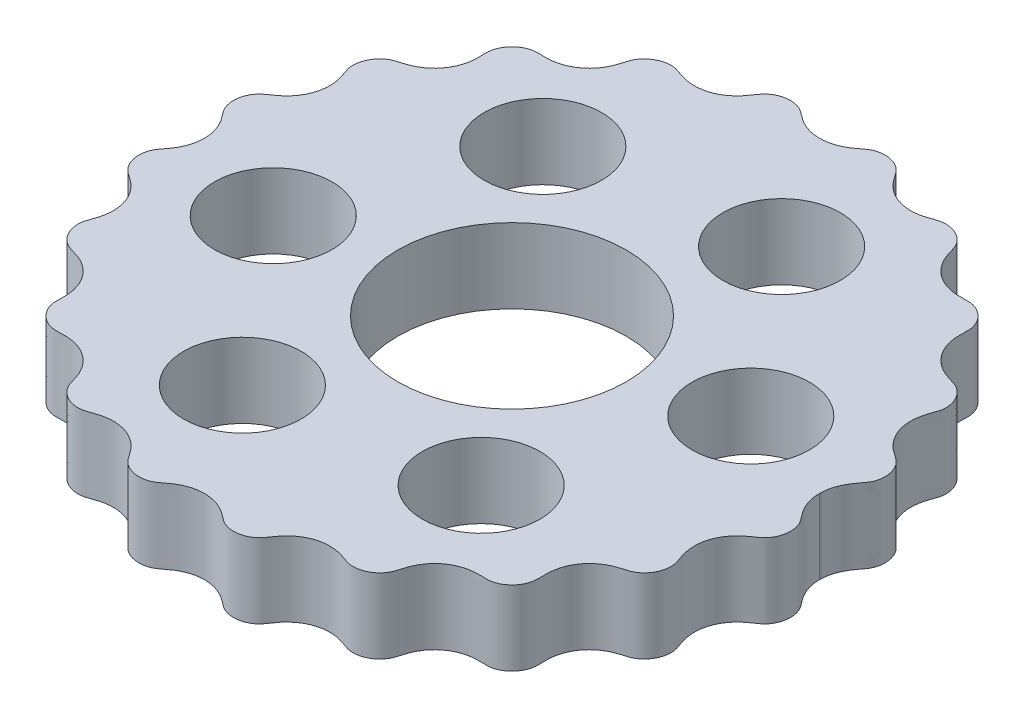
SolidWorks part; units mm, degrees
ref_plane "Front Plane" through (0, 0, 0) normal (0, 0, 1) x (1, 0, 0)
ref_plane "Top Plane" through (0, 0, 0) normal (0, 1, 0) x (1, 0, 0)
ref_plane "Right Plane" through (0, 0, 0) normal (1, 0, 0) x (0, 0, -1)
sketch "Sketch1" plane through (0, 0, 0) normal (0, 1, 0) x (1, 0, 0)
  circle A0 centre (0, 0) radius 10.4
  spline S0 degree 4 poles (26.8059, 13.4572) (26.8639, 13.3205) (26.9582, 13.0381) (27.0247, 12.6393) (26.9913, 12.1833) (26.8931, 11.8403) (26.7874, 11.5481) (26.6811, 11.2558) (26.5654, 10.8802) (26.4695, 10.4144) (26.427, 9.9103) (26.4544, 9.3746) (26.5579, 8.8368) (26.741, 8.3075) (27.0736, 7.6723) (27.5036, 7.1396) (27.9833, 6.7262) (28.4638, 6.3979) (28.7892, 6.1843) (29.1138, 5.8878) (29.3918, 5.4852) (29.5767, 5.0325) (29.6654, 4.5525) (29.6681, 4.114) (29.6085, 3.728) (29.4888, 3.368) (29.3103, 3.046) (29.0925, 2.7659) (28.8808, 2.4963) (28.6821, 2.2162) (28.5035, 1.9231) (28.3483, 1.6165) (28.2193, 1.2987) (28.1286, 1.0033) (28.0684, 0.7391) (28.031, 0.4991) (28.0098, 0.3153) (27.9999, 0.0887) (27.9991, -0.0272) (28.0029, -0.1486) (28.0089, -0.265) (28.0175, -0.3782) (28.0354, -0.5324) (28.0698, -0.744) (28.1249, -0.9884) (28.2083, -1.2608) (28.3108, -1.5275) (28.4323, -1.7855) (28.5865, -2.0656) (28.7812, -2.3612) (29.0137, -2.6715) (29.2824, -2.9979) (29.5111, -3.3993) (29.6506, -3.8796) (29.6859, -4.4152) (29.5951, -4.9837) (29.3933, -5.4827) (29.1084, -5.8975) (28.762, -6.2072) (28.4035, -6.4354) (28.0263, -6.7018) (27.6432, -7.0237) (27.1801, -7.5243) (26.7185, -8.267) (26.4119, -9.2525) (26.4126, -10.2383) (26.5911, -11.0032) (26.7882, -11.5548) (26.927, -11.9205) (27.0435, -12.4984) (26.9493, -13.2923) (26.5792, -14.0112) (25.9799, -14.554) (25.4261, -14.7937) (25.0319, -14.8958) (24.5986, -15.0296) (24.1341, -15.2147) (23.6554, -15.4803) (23.1843, -15.841) (22.6738, -16.3739) (22.2038, -17.1251) (21.9508, -17.9268) (21.889, -18.705) (21.9078, -19.2869) (21.9249, -19.6752) (21.8711, -20.1112) (21.7056, -20.5711) (21.3378, -21.1537) (20.842, -21.5737) (20.3424, -21.8097) (19.8501, -21.9053) (19.5428, -21.9221) (19.1848, -21.902) (18.7291, -21.8953) (18.227, -21.9313) (17.5411, -22.0688) (16.7174, -22.4135) (15.8912, -23.0484) (15.3236, -23.8571) (15.0299, -24.5755) (14.8707, -25.1317) (14.766, -25.5035) (14.5781, -25.8973) (14.2781, -26.2796) (13.8632, -26.6219) (13.3335, -26.8852) (12.7989, -27.0092) (12.2906, -27.0113) (11.8436, -26.9022) (11.4606, -26.7512) (11.0257, -26.6054) (10.534, -26.4858) (9.8342, -26.4087) (8.9432, -26.4893) (8.1017, -26.7955) (7.3751, -27.2965) (6.9023, -27.7769) (6.6066, -28.1555) (6.3661, -28.5133) (6.1518, -28.8317) (5.8503, -29.1436) (5.4485, -29.4103) (4.9529, -29.6037) (4.3781, -29.688) (3.8872, -29.6483) (3.4999, -29.5378) (3.2176, -29.4051) (3.0274, -29.2892) (2.8036, -29.124) (2.5433, -28.9157) (2.201, -28.6662) (1.7577, -28.406) (1.2527, -28.191) (0.6884, -28.0437) (-0.0326, -27.9684) (-0.7557, -28.0384) (-1.4479, -28.2507) (-2.0404, -28.5633) (-2.4351, -28.8321) (-2.7715, -29.0973) (-3.073, -29.3309) (-3.4554, -29.5298) (-3.9177, -29.6561) (-4.4471, -29.6846) (-5.0196, -29.5854) (-5.5263, -29.3716) (-5.9011, -29.0996) (-6.1494, -28.8243) (-6.3429, -28.5502) (-6.5277, -28.2703) (-6.7787, -27.9261) (-7.1239, -27.5413) (-7.5425, -27.1814) (-8.039, -26.8689) (-8.7082, -26.5782) (-9.4242, -26.4275) (-10.1535, -26.4235) (-10.8129, -26.5457) (-11.2651, -26.6821) (-11.6572, -26.8284) (-12.0036, -26.9493) (-12.4193, -27.0163) (-12.8932, -26.9935) (-13.4055, -26.8567) (-13.9224, -26.5824) (-14.2973, -26.2558) (-14.5452, -25.9324) (-14.6935, -25.6538) (-14.7772, -25.4447) (-14.8598, -25.1759) (-14.9496, -24.8509) (-15.0843, -24.4441) (-15.2974, -23.9699) (-15.5891, -23.4974) (-15.9703, -23.0471) (-16.413, -22.6624) (-16.906, -22.3515) (-17.4366, -22.1197) (-17.9918, -21.9687) (-18.5102, -21.9036) (-18.9796, -21.8955) (-19.3952, -21.9141) (-19.7601, -21.9199) (-20.1734, -21.8522) (-20.6133, -21.6828) (-21.056, -21.3934) (-21.4613, -20.9716) (-21.716, -20.5431) (-21.8505, -20.1561) (-21.9036, -19.8431) (-21.9171, -19.6171) (-21.9114, -19.3343) (-21.8968, -18.9956) (-21.9008, -18.5646) (-21.96, -18.0451) (-22.0957, -17.5034) (-22.3246, -16.9559) (-22.6319, -16.4545) (-23.0085, -16.01) (-23.4431, -15.6306) (-23.9235, -15.3209) (-24.3946, -15.103) (-24.8364, -14.9529) (-25.2353, -14.8436) (-25.5816, -14.7347) (-25.9501, -14.5407) (-26.3123, -14.2435) (-26.6414, -13.8314) (-26.8948, -13.3044) (-27.0029, -12.8166) (-27.0091, -12.4045) (-26.9605, -12.0891) (-26.9016, -11.8691) (-26.8075, -11.6008) (-26.6887, -11.2811) (-26.5601, -10.8672) (-26.458, -10.3514) (-26.4232, -9.7908) (-26.4764, -9.1964) (-26.6191, -8.6243) (-26.8445, -8.0873) (-27.1437, -7.5965) (-27.5055, -7.1591) (-27.8858, -6.8108) (-28.2582, -6.5346) (-28.6022, -6.3092) (-28.8951, -6.0977) (-29.1816, -5.7989) (-29.4306, -5.4054) (-29.6132, -4.914) (-29.6894, -4.3381) (-29.6413, -3.8421) (-29.519, -3.4476) (-29.3472, -3.1076) (-29.1769, -2.8701) (-28.9943, -2.6435) (-28.7849, -2.3635) (-28.5715, -2.0475) (-28.3452, -1.633) (-28.1436, -1.1074) (-28.017, -0.526) (-27.9819, 0.0602) (-28.0354, 0.6372) (-28.1721, 1.192) (-28.3833, 1.7148) (-28.6382, 2.1591) (-28.9068, 2.5335) (-29.1632, 2.852) (-29.3734, 3.1437) (-29.5496, 3.5157) (-29.6618, 3.9648) (-29.6814, 4.4871) (-29.5742, 5.058) (-29.3729, 5.515) (-29.1317, 5.8532) (-28.9013, 6.0815) (-28.7173, 6.227) (-28.5238, 6.3592) (-28.3295, 6.4899) (-28.0903, 6.6589) (-27.7891, 6.8963) (-27.4455, 7.2241) (-27.0924, 7.6666) (-26.7946, 8.1855) (-26.5842, 8.7353) (-26.4618, 9.3014) (-26.4252, 9.8696) (-26.4682, 10.4278) (-26.5754, 10.9253) (-26.7159, 11.361) (-26.8609, 11.741) (-26.9676, 12.0823) (-27.0169, 12.4888) (-26.9825, 12.9476) (-26.8522, 13.4002) (-26.6322, 13.8255) (-26.3658, 14.1732) (-26.0763, 14.4443) (-25.7467, 14.6606) (-25.3843, 14.804) (-25.0132, 14.9019) (-24.6498, 15.0143) (-24.2055, 15.1839) (-23.698, 15.4481) (-23.1928, 15.8218) (-22.7276, 16.321) (-22.3767, 16.8567) (-22.1301, 17.403) (-21.9781, 17.9494) (-21.914, 18.4208) (-21.8983, 18.8047) (-21.9019, 19.0981) (-21.9104, 19.3326) (-21.9174, 19.5673) (-21.9082, 19.8021) (-21.8596, 20.1234) (-21.7283, 20.5183) (-21.4773, 20.9505) (-21.0789, 21.3732) (-20.6456, 21.6645) (-20.2176, 21.8382) (-19.814, 21.9152) (-19.4551, 21.9175) (-19.0475, 21.8972) (-18.5877, 21.8993) (-18.0794, 21.9532) (-17.5333, 22.0879) (-17.0042, 22.3017) (-16.5051, 22.596) (-16.0501, 22.968) (-15.6523, 23.412) (-15.3437, 23.8842) (-15.1405, 24.3114) (-15.0092, 24.6702) (-14.9231, 24.9491) (-14.8593, 25.1735) (-14.7931, 25.3975) (-14.7109, 25.6163) (-14.5642, 25.9042) (-14.3169, 26.2361) (-13.9442, 26.5673) (-13.4337, 26.8447) (-12.9296, 26.9863) (-12.4659, 27.0169) (-12.0563, 26.962) (-11.7134, 26.8503) (-11.3296, 26.7046) (-10.8884, 26.5654) (-10.3845, 26.4617) (-9.8193, 26.4248) (-9.2469, 26.4696) (-8.6797, 26.6011) (-8.1319, 26.8206) (-7.6179, 27.1262) (-7.1833, 27.4836) (-6.8246, 27.8695) (-6.5644, 28.2171) (-6.3751, 28.5015) (-6.2133, 28.736) (-6.0701, 28.9136) (-5.8435, 29.1393) (-5.5063, 29.3776) (-5.048, 29.5776) (-4.4728, 29.6829) (-3.9465, 29.6597) (-3.4939, 29.5424) (-3.1206, 29.3597) (-2.829, 29.1445) (-2.5068, 28.8863) (-2.1269, 28.6173) (-1.6752, 28.3639) (-1.144, 28.1564) (-0.5827, 28.0264) (-0.0019, 27.9813) (0.585, 28.0256) (1.164, 28.1611) (1.6834, 28.3689) (2.1399, 28.6261) (2.4919, 28.8762) (2.758, 29.0874) (2.9836, 29.2588) (3.1745, 29.3814) (3.4591, 29.5233) (3.8519, 29.643) (4.3485, 29.6895) (4.928, 29.6101) (5.4221, 29.4229) (5.8174, 29.1679) (6.1153, 28.8747) (6.3254, 28.5771) (6.5539, 28.2304) (6.8352, 27.8558) (7.1911, 27.4748) (7.6377, 27.1141) (8.1357, 26.8201) (8.6763, 26.6024) (9.2478, 26.4685) (9.8372, 26.4232) (10.3921, 26.4637) (10.9022, 26.5694) (11.3114, 26.6993) (11.6278, 26.8177) (11.8942, 26.9095) (12.1129, 26.9653) (12.4259, 27.0099) (12.834, 27.0001) (13.3192, 26.8894) (13.8452, 26.633) (14.257, 26.2998) (14.554, 25.9312) (14.7449, 25.5566) (14.8512, 25.2062) (14.9628, 24.8038) (15.1173, 24.3584) (15.4041, 23.754) (15.8339, 23.1659) (16.3749, 22.674) (17.0026, 22.3015) (17.5477, 22.0817) (18.0857, 21.9531) (18.6008, 21.899) (19.0277, 21.8976) (19.3633, 21.9128) (19.6435, 21.9166) (19.8673, 21.9006) (20.1767, 21.8445) (20.5589, 21.7078) (20.9822, 21.4527) (21.3992, 21.0485) (21.6877, 20.6041) (21.8577, 20.1572) (21.9226, 19.7321) (21.9116, 19.3517) (21.8945, 18.9246) (21.9082, 18.4482) (22.0019, 17.7864) (22.2349, 17.1018) (22.6013, 16.4748) (23.0847, 15.9341) (23.5355, 15.5623) (24.0065, 15.2784) (24.4781, 15.0715) (24.8818, 14.9405) (25.204, 14.8521) (25.4698, 14.7684) (25.6759, 14.683) (25.9502, 14.533) (26.2682, 14.2846) (26.5897, 13.9109) (26.8599, 13.3967) (26.9953, 12.8828) (27.0165, 12.402) (26.9428, 11.9755) (26.812, 11.6155) (26.6639, 11.2117) (26.531, 10.751) (26.419, 10.0878) (26.4384, 9.206) (26.6828, 8.3445) (27.1397, 7.5745) (27.6133, 7.0515) (27.9992, 6.7228) (28.3732, 6.4556) (28.7212, 6.2343) (29.0737, 5.9372) (29.3722, 5.5245) (29.587, 5.0189) (29.6859, 4.4357) (29.6537, 3.8993) (29.5217, 3.4328) (29.3154, 3.0494) (29.0766, 2.7466) (28.855, 2.4624) (28.6625, 2.1852) (28.5017, 1.9165) (28.3697, 1.659) (28.2562, 1.3927) (28.1621, 1.1193) (28.0976, 0.8742) (28.0555, 0.6601) (28.0321, 0.5046) (28.0196, 0.391) (28.0097, 0.2731) (28.0019, 0.1501) (27.999, 0.0339) (28.0017, -0.1944) (28.0172, -0.3789) (28.0404, -0.5678) (28.0694, -0.7323) (28.1083, -0.9116) (28.1593, -1.1041) (28.2315, -1.325) (28.3306, -1.5714) (28.4456, -1.8108) (28.6076, -2.1005) (28.7998, -2.3889) (29.0195, -2.6747) (29.2526, -2.9684) (29.4251, -3.2427) (29.5712, -3.5902) (29.6646, -4.0094) (29.6814, -4.6356) (29.5182, -5.2632) (29.2112, -5.7976) (28.789, -6.1854) (28.4595, -6.4) (28.104, -6.6445) (27.7365, -6.9392) (27.2807, -7.3993) (26.8581, -8.016) (26.5516, -8.7634) (26.4156, -9.6155) (26.4446, -10.2999) (26.5611, -10.8731) (26.6969, -11.301) (26.8049, -11.5957) (26.9184, -11.9123) (27.0024, -12.2627) (27.015, -12.6849) (26.9522, -13.0399) (26.88, -13.2686) (26.8371, -13.3802) knots 0 0 0 0 0 0.002533 0.005066 0.006835 0.00772 0.008605 0.010374 0.012143 0.014424 0.016705 0.018986 0.021267 0.023746 0.026226 0.031185 0.032844 0.034503 0.036162 0.037822 0.040301 0.04278 0.04444 0.046099 0.047759 0.049418 0.050882 0.052346 0.05381 0.055273 0.056737 0.058201 0.059665 0.061129 0.06199 0.062852 0.063714 0.064575 0.065184 0.065488 0.065792 0.0664 0.067009 0.068226 0.069443 0.07066 0.071876 0.073093 0.07431 0.076111 0.077913 0.079714 0.081515 0.083942 0.086368 0.088809 0.09125 0.093062 0.094873 0.096685 0.098497 0.100945 0.103394 0.108291 0.113293 0.118294 0.119961 0.121629 0.123296 0.124963 0.129954 0.134964 0.136702 0.138439 0.140177 0.141915 0.144438 0.146961 0.149485 0.152008 0.156981 0.161954 0.163611 0.165267 0.166924 0.16858 0.17106 0.17354 0.178581 0.179454 0.180328 0.182075 0.183822 0.18557 0.188108 0.190647 0.195724 0.200669 0.205614 0.20726 0.208906 0.210552 0.212197 0.214662 0.217127 0.219662 0.222197 0.223954 0.225711 0.227468 0.229224 0.231778 0.234332 0.23944 0.244357 0.246816 0.249274 0.250909 0.252544 0.254179 0.255814 0.258264 0.260713 0.263181 0.265648 0.266597 0.267546 0.268495 0.269443 0.271341 0.273239 0.275718 0.278197 0.280677 0.283156 0.288045 0.290489 0.292933 0.294557 0.296182 0.297806 0.299431 0.301865 0.304299 0.306781 0.309263 0.311171 0.312126 0.31308 0.314988 0.316897 0.319391 0.321884 0.324378 0.326872 0.331797 0.33426 0.336723 0.338285 0.339847 0.34141 0.342972 0.345429 0.347885 0.350381 0.352878 0.353837 0.354797 0.355756 0.356716 0.358635 0.360555 0.363063 0.365571 0.368079 0.370587 0.373034 0.37548 0.377927 0.380373 0.381927 0.383481 0.385035 0.386588 0.38903 0.391471 0.393982 0.396492 0.397457 0.398422 0.399387 0.400352 0.402282 0.404212 0.406735 0.409257 0.411779 0.414302 0.416732 0.419162 0.421593 0.424023 0.425568 0.427114 0.42866 0.430205 0.432631 0.435057 0.437582 0.440106 0.441077 0.442047 0.443017 0.443988 0.445929 0.44787 0.450406 0.452943 0.455479 0.458016 0.46043 0.462844 0.465258 0.467672 0.469209 0.470747 0.472284 0.473822 0.476232 0.478643 0.481152 0.483661 0.484655 0.485649 0.487638 0.488632 0.489626 0.491615 0.494144 0.496673 0.499201 0.50173 0.504128 0.506525 0.508923 0.51132 0.51285 0.514379 0.515909 0.517438 0.519834 0.522229 0.524752 0.527275 0.528275 0.529275 0.530274 0.531274 0.532274 0.533273 0.535273 0.537816 0.540358 0.542901 0.545444 0.547825 0.550206 0.552587 0.554968 0.556489 0.558011 0.559533 0.561055 0.563435 0.565816 0.567502 0.569188 0.570875 0.572561 0.574183 0.575806 0.577428 0.579051 0.582295 0.58554 0.588087 0.590635 0.593182 0.595729 0.597733 0.598734 0.599736 0.600737 0.601739 0.60274 0.603742 0.60627 0.608797 0.611188 0.613578 0.615105 0.616632 0.618159 0.619686 0.622078 0.624469 0.626861 0.629253 0.631787 0.63432 0.636854 0.639387 0.64138 0.642376 0.643372 0.644368 0.645364 0.64636 0.647356 0.64987 0.652383 0.654789 0.657195 0.658729 0.660264 0.661799 0.663334 0.665742 0.66815 0.670559 0.672967 0.675509 0.67805 0.680591 0.683133 0.685077 0.687022 0.687994 0.688966 0.689939 0.690911 0.69344 0.695969 0.69839 0.700811 0.702354 0.703897 0.70544 0.706982 0.709407 0.711832 0.714257 0.716681 0.719208 0.721736 0.724263 0.72679 0.728724 0.730658 0.731624 0.732591 0.733558 0.734525 0.73704 0.739555 0.741992 0.744428 0.745979 0.74753 0.749081 0.750632 0.753073 0.755514 0.757955 0.760396 0.762909 0.765422 0.767935 0.770448 0.772371 0.774294 0.775255 0.776216 0.777178 0.778139 0.78064 0.783141 0.785593 0.788044 0.789604 0.791163 0.792722 0.794282 0.796739 0.799196 0.804111 0.806609 0.809108 0.811607 0.814105 0.816018 0.81793 0.818886 0.819842 0.820798 0.821754 0.824241 0.826727 0.829157 0.831586 0.833207 0.834828 0.836448 0.838069 0.840509 0.842948 0.847826 0.850311 0.852795 0.855279 0.857763 0.859665 0.861566 0.862517 0.863468 0.864418 0.865369 0.867841 0.870314 0.872758 0.875202 0.876833 0.878465 0.880096 0.881728 0.884181 0.886635 0.891542 0.896661 0.89922 0.901779 0.903539 0.905299 0.907059 0.908819 0.91136 0.9139 0.91636 0.918819 0.920461 0.922103 0.923745 0.925387 0.926621 0.927855 0.929089 0.930323 0.931557 0.932791 0.933407 0.934024 0.934333 0.934641 0.935258 0.936122 0.936987 0.937851 0.938715 0.939281 0.939847 0.94098 0.942112 0.943245 0.944377 0.94551 0.947775 0.949153 0.950531 0.951909 0.953287 0.955556 0.957826 0.96251 0.964186 0.965863 0.96754 0.969216 0.971553 0.97389 0.978563 0.981882 0.9852 0.988519 0.990178 0.991837 0.992858 0.993878 0.995919 0.997959 1 1 1 1 1 construction
  spline S1 degree 4 poles (28, 0) (28, -0.031) (28.0007, -0.0776) (28.0029, -0.1486) (28.0089, -0.265) (28.0175, -0.3782) (28.0354, -0.5324) (28.0698, -0.744) (28.1249, -0.9884) (28.2083, -1.2608) (28.3108, -1.5275) (28.4323, -1.7855) (28.5865, -2.0656) (28.7812, -2.3612) (29.0137, -2.6715) (29.2824, -2.9979) (29.5111, -3.3993) (29.6506, -3.8796) (29.6859, -4.4152) (29.5951, -4.9837) (29.3933, -5.4827) (29.1084, -5.8975) (28.762, -6.2072) (28.4035, -6.4354) (28.0263, -6.7018) (27.6432, -7.0237) (27.1801, -7.5243) (26.7185, -8.267) (26.4119, -9.2525) (26.4126, -10.2383) (26.5911, -11.0032) (26.7882, -11.5548) (26.927, -11.9205) (27.0435, -12.4984) (26.9493, -13.2923) (26.5792, -14.0112) (25.9799, -14.554) (25.4261, -14.7937) (25.0319, -14.8958) (24.5986, -15.0296) (24.1341, -15.2147) (23.6554, -15.4803) (23.1843, -15.841) (22.6738, -16.3739) (22.2038, -17.1251) (21.9508, -17.9268) (21.889, -18.705) (21.9078, -19.2869) (21.9249, -19.6752) (21.8711, -20.1112) (21.7056, -20.5711) (21.3378, -21.1537) (20.842, -21.5737) (20.3424, -21.8097) (19.8501, -21.9053) (19.5428, -21.9221) (19.1848, -21.902) (18.7291, -21.8953) (18.227, -21.9313) (17.5411, -22.0688) (16.7174, -22.4135) (15.8912, -23.0484) (15.3236, -23.8571) (15.0299, -24.5755) (14.8707, -25.1317) (14.766, -25.5035) (14.5781, -25.8973) (14.2781, -26.2796) (13.8632, -26.6219) (13.3335, -26.8852) (12.7989, -27.0092) (12.2906, -27.0113) (11.8436, -26.9022) (11.4606, -26.7512) (11.0257, -26.6054) (10.534, -26.4858) (9.8342, -26.4087) (8.9432, -26.4893) (8.1017, -26.7955) (7.3751, -27.2965) (6.9023, -27.7769) (6.6066, -28.1555) (6.3661, -28.5133) (6.1518, -28.8317) (5.8503, -29.1436) (5.4485, -29.4103) (4.9529, -29.6037) (4.3781, -29.688) (3.8872, -29.6483) (3.4999, -29.5378) (3.2176, -29.4051) (3.0274, -29.2892) (2.8036, -29.124) (2.5433, -28.9157) (2.201, -28.6662) (1.7577, -28.406) (1.2527, -28.191) (0.6884, -28.0437) (-0.0326, -27.9684) (-0.7557, -28.0384) (-1.4479, -28.2507) (-2.0404, -28.5633) (-2.4351, -28.8321) (-2.7715, -29.0973) (-3.073, -29.3309) (-3.4554, -29.5298) (-3.9177, -29.6561) (-4.4471, -29.6846) (-5.0196, -29.5854) (-5.5263, -29.3716) (-5.9011, -29.0996) (-6.1494, -28.8243) (-6.3429, -28.5502) (-6.5277, -28.2703) (-6.7787, -27.9261) (-7.1239, -27.5413) (-7.5425, -27.1814) (-8.039, -26.8689) (-8.7082, -26.5782) (-9.4242, -26.4275) (-10.1535, -26.4235) (-10.8129, -26.5457) (-11.2651, -26.6821) (-11.6572, -26.8284) (-12.0036, -26.9493) (-12.4193, -27.0163) (-12.8932, -26.9935) (-13.4055, -26.8567) (-13.9224, -26.5824) (-14.2973, -26.2558) (-14.5452, -25.9324) (-14.6935, -25.6538) (-14.7772, -25.4447) (-14.8598, -25.1759) (-14.9496, -24.8509) (-15.0843, -24.4441) (-15.2974, -23.9699) (-15.5891, -23.4974) (-15.9703, -23.0471) (-16.413, -22.6624) (-16.906, -22.3515) (-17.4366, -22.1197) (-17.9918, -21.9687) (-18.5102, -21.9036) (-18.9796, -21.8955) (-19.3952, -21.9141) (-19.7601, -21.9199) (-20.1734, -21.8522) (-20.6133, -21.6828) (-21.056, -21.3934) (-21.4613, -20.9716) (-21.716, -20.5431) (-21.8505, -20.1561) (-21.9036, -19.8431) (-21.9171, -19.6171) (-21.9114, -19.3343) (-21.8968, -18.9956) (-21.9008, -18.5646) (-21.96, -18.0451) (-22.0957, -17.5034) (-22.3246, -16.9559) (-22.6319, -16.4545) (-23.0085, -16.01) (-23.4431, -15.6306) (-23.9235, -15.3209) (-24.3946, -15.103) (-24.8364, -14.9529) (-25.2353, -14.8436) (-25.5816, -14.7347) (-25.9501, -14.5407) (-26.3123, -14.2435) (-26.6414, -13.8314) (-26.8948, -13.3044) (-27.0029, -12.8166) (-27.0091, -12.4045) (-26.9605, -12.0891) (-26.9016, -11.8691) (-26.8075, -11.6008) (-26.6887, -11.2811) (-26.5601, -10.8672) (-26.458, -10.3514) (-26.4232, -9.7908) (-26.4764, -9.1964) (-26.6191, -8.6243) (-26.8445, -8.0873) (-27.1437, -7.5965) (-27.5055, -7.1591) (-27.8858, -6.8108) (-28.2582, -6.5346) (-28.6022, -6.3092) (-28.8951, -6.0977) (-29.1816, -5.7989) (-29.4306, -5.4054) (-29.6132, -4.914) (-29.6894, -4.3381) (-29.6413, -3.8421) (-29.519, -3.4476) (-29.3472, -3.1076) (-29.1769, -2.8701) (-28.9943, -2.6435) (-28.7849, -2.3635) (-28.5715, -2.0475) (-28.3452, -1.633) (-28.1436, -1.1074) (-28.017, -0.526) (-27.9819, 0.0602) (-28.0354, 0.6372) (-28.1721, 1.192) (-28.3833, 1.7148) (-28.6382, 2.1591) (-28.9068, 2.5335) (-29.1632, 2.852) (-29.3734, 3.1437) (-29.5496, 3.5157) (-29.6618, 3.9648) (-29.6814, 4.4871) (-29.5742, 5.058) (-29.3729, 5.515) (-29.1317, 5.8532) (-28.9013, 6.0815) (-28.7173, 6.227) (-28.5238, 6.3592) (-28.3295, 6.4899) (-28.0903, 6.6589) (-27.7891, 6.8963) (-27.4455, 7.2241) (-27.0924, 7.6666) (-26.7946, 8.1855) (-26.5842, 8.7353) (-26.4618, 9.3014) (-26.4252, 9.8696) (-26.4682, 10.4278) (-26.5754, 10.9253) (-26.7159, 11.361) (-26.8609, 11.741) (-26.9676, 12.0823) (-27.0169, 12.4888) (-26.9825, 12.9476) (-26.8522, 13.4002) (-26.6322, 13.8255) (-26.3658, 14.1732) (-26.0763, 14.4443) (-25.7467, 14.6606) (-25.3843, 14.804) (-25.0132, 14.9019) (-24.6498, 15.0143) (-24.2055, 15.1839) (-23.698, 15.4481) (-23.1928, 15.8218) (-22.7276, 16.321) (-22.3767, 16.8567) (-22.1301, 17.403) (-21.9781, 17.9494) (-21.914, 18.4208) (-21.8983, 18.8047) (-21.9019, 19.0981) (-21.9104, 19.3326) (-21.9174, 19.5673) (-21.9082, 19.8021) (-21.8596, 20.1234) (-21.7283, 20.5183) (-21.4773, 20.9505) (-21.0789, 21.3732) (-20.6456, 21.6645) (-20.2176, 21.8382) (-19.814, 21.9152) (-19.4551, 21.9175) (-19.0475, 21.8972) (-18.5877, 21.8993) (-18.0794, 21.9532) (-17.5333, 22.0879) (-17.0042, 22.3017) (-16.5051, 22.596) (-16.0501, 22.968) (-15.6523, 23.412) (-15.3437, 23.8842) (-15.1405, 24.3114) (-15.0092, 24.6702) (-14.9231, 24.9491) (-14.8593, 25.1735) (-14.7931, 25.3975) (-14.7109, 25.6163) (-14.5642, 25.9042) (-14.3169, 26.2361) (-13.9442, 26.5673) (-13.4337, 26.8447) (-12.9296, 26.9863) (-12.4659, 27.0169) (-12.0563, 26.962) (-11.7134, 26.8503) (-11.3296, 26.7046) (-10.8884, 26.5654) (-10.3845, 26.4617) (-9.8193, 26.4248) (-9.2469, 26.4696) (-8.6797, 26.6011) (-8.1319, 26.8206) (-7.6179, 27.1262) (-7.1833, 27.4836) (-6.8246, 27.8695) (-6.5644, 28.2171) (-6.3751, 28.5015) (-6.2133, 28.736) (-6.0701, 28.9136) (-5.8435, 29.1393) (-5.5063, 29.3776) (-5.048, 29.5776) (-4.4728, 29.6829) (-3.9465, 29.6597) (-3.4939, 29.5424) (-3.1206, 29.3597) (-2.829, 29.1445) (-2.5068, 28.8863) (-2.1269, 28.6173) (-1.6752, 28.3639) (-1.144, 28.1564) (-0.5827, 28.0264) (-0.0019, 27.9813) (0.585, 28.0256) (1.164, 28.1611) (1.6834, 28.3689) (2.1399, 28.6261) (2.4919, 28.8762) (2.758, 29.0874) (2.9836, 29.2588) (3.1745, 29.3814) (3.4591, 29.5233) (3.8519, 29.643) (4.3485, 29.6895) (4.928, 29.6101) (5.4221, 29.4229) (5.8174, 29.1679) (6.1153, 28.8747) (6.3254, 28.5771) (6.5539, 28.2304) (6.8352, 27.8558) (7.1911, 27.4748) (7.6377, 27.1141) (8.1357, 26.8201) (8.6763, 26.6024) (9.2478, 26.4685) (9.8372, 26.4232) (10.3921, 26.4637) (10.9022, 26.5694) (11.3114, 26.6993) (11.6278, 26.8177) (11.8942, 26.9095) (12.1129, 26.9653) (12.4259, 27.0099) (12.834, 27.0001) (13.3192, 26.8894) (13.8452, 26.633) (14.257, 26.2998) (14.554, 25.9312) (14.7449, 25.5566) (14.8512, 25.2062) (14.9628, 24.8038) (15.1173, 24.3584) (15.4041, 23.754) (15.8339, 23.1659) (16.3749, 22.674) (17.0026, 22.3015) (17.5477, 22.0817) (18.0857, 21.9531) (18.6008, 21.899) (19.0277, 21.8976) (19.3633, 21.9128) (19.6435, 21.9166) (19.8673, 21.9006) (20.1767, 21.8445) (20.5589, 21.7078) (20.9822, 21.4527) (21.3992, 21.0485) (21.6877, 20.6041) (21.8577, 20.1572) (21.9226, 19.7321) (21.9116, 19.3517) (21.8945, 18.9246) (21.9082, 18.4482) (22.0019, 17.7864) (22.2349, 17.1018) (22.6013, 16.4748) (23.0847, 15.9341) (23.5355, 15.5623) (24.0065, 15.2784) (24.4781, 15.0715) (24.8818, 14.9405) (25.204, 14.8521) (25.4698, 14.7684) (25.6759, 14.683) (25.9502, 14.533) (26.2682, 14.2846) (26.5897, 13.9109) (26.8599, 13.3967) (26.9953, 12.8828) (27.0165, 12.402) (26.9428, 11.9755) (26.812, 11.6155) (26.6639, 11.2117) (26.531, 10.751) (26.419, 10.0878) (26.4384, 9.206) (26.6828, 8.3445) (27.1397, 7.5745) (27.6133, 7.0515) (27.9992, 6.7228) (28.3732, 6.4556) (28.7212, 6.2343) (29.0737, 5.9372) (29.3722, 5.5245) (29.587, 5.0189) (29.6859, 4.4357) (29.6537, 3.8993) (29.5217, 3.4328) (29.3154, 3.0494) (29.0766, 2.7466) (28.855, 2.4624) (28.6625, 2.1852) (28.5017, 1.9165) (28.3697, 1.659) (28.2562, 1.3927) (28.1621, 1.1193) (28.0976, 0.8742) (28.0555, 0.6601) (28.0321, 0.5046) (28.0196, 0.391) (28.0097, 0.2731) (28.0051, 0.2008) (28.003, 0.1536) (28.002, 0.1221) knots 0.064575 0.064575 0.064575 0.064575 0.064575 0.065184 0.065488 0.065792 0.0664 0.067009 0.068226 0.069443 0.07066 0.071876 0.073093 0.07431 0.076111 0.077913 0.079714 0.081515 0.083942 0.086368 0.088809 0.09125 0.093062 0.094873 0.096685 0.098497 0.100945 0.103394 0.108291 0.113293 0.118294 0.119961 0.121629 0.123296 0.124963 0.129954 0.134964 0.136702 0.138439 0.140177 0.141915 0.144438 0.146961 0.149485 0.152008 0.156981 0.161954 0.163611 0.165267 0.166924 0.16858 0.17106 0.17354 0.178581 0.179454 0.180328 0.182075 0.183822 0.18557 0.188108 0.190647 0.195724 0.200669 0.205614 0.20726 0.208906 0.210552 0.212197 0.214662 0.217127 0.219662 0.222197 0.223954 0.225711 0.227468 0.229224 0.231778 0.234332 0.23944 0.244357 0.246816 0.249274 0.250909 0.252544 0.254179 0.255814 0.258264 0.260713 0.263181 0.265648 0.266597 0.267546 0.268495 0.269443 0.271341 0.273239 0.275718 0.278197 0.280677 0.283156 0.288045 0.290489 0.292933 0.294557 0.296182 0.297806 0.299431 0.301865 0.304299 0.306781 0.309263 0.311171 0.312126 0.31308 0.314988 0.316897 0.319391 0.321884 0.324378 0.326872 0.331797 0.33426 0.336723 0.338285 0.339847 0.34141 0.342972 0.345429 0.347885 0.350381 0.352878 0.353837 0.354797 0.355756 0.356716 0.358635 0.360555 0.363063 0.365571 0.368079 0.370587 0.373034 0.37548 0.377927 0.380373 0.381927 0.383481 0.385035 0.386588 0.38903 0.391471 0.393982 0.396492 0.397457 0.398422 0.399387 0.400352 0.402282 0.404212 0.406735 0.409257 0.411779 0.414302 0.416732 0.419162 0.421593 0.424023 0.425568 0.427114 0.42866 0.430205 0.432631 0.435057 0.437582 0.440106 0.441077 0.442047 0.443017 0.443988 0.445929 0.44787 0.450406 0.452943 0.455479 0.458016 0.46043 0.462844 0.465258 0.467672 0.469209 0.470747 0.472284 0.473822 0.476232 0.478643 0.481152 0.483661 0.484655 0.485649 0.487638 0.488632 0.489626 0.491615 0.494144 0.496673 0.499201 0.50173 0.504128 0.506525 0.508923 0.51132 0.51285 0.514379 0.515909 0.517438 0.519834 0.522229 0.524752 0.527275 0.528275 0.529275 0.530274 0.531274 0.532274 0.533273 0.535273 0.537816 0.540358 0.542901 0.545444 0.547825 0.550206 0.552587 0.554968 0.556489 0.558011 0.559533 0.561055 0.563435 0.565816 0.567502 0.569188 0.570875 0.572561 0.574183 0.575806 0.577428 0.579051 0.582295 0.58554 0.588087 0.590635 0.593182 0.595729 0.597733 0.598734 0.599736 0.600737 0.601739 0.60274 0.603742 0.60627 0.608797 0.611188 0.613578 0.615105 0.616632 0.618159 0.619686 0.622078 0.624469 0.626861 0.629253 0.631787 0.63432 0.636854 0.639387 0.64138 0.642376 0.643372 0.644368 0.645364 0.64636 0.647356 0.64987 0.652383 0.654789 0.657195 0.658729 0.660264 0.661799 0.663334 0.665742 0.66815 0.670559 0.672967 0.675509 0.67805 0.680591 0.683133 0.685077 0.687022 0.687994 0.688966 0.689939 0.690911 0.69344 0.695969 0.69839 0.700811 0.702354 0.703897 0.70544 0.706982 0.709407 0.711832 0.714257 0.716681 0.719208 0.721736 0.724263 0.72679 0.728724 0.730658 0.731624 0.732591 0.733558 0.734525 0.73704 0.739555 0.741992 0.744428 0.745979 0.74753 0.749081 0.750632 0.753073 0.755514 0.757955 0.760396 0.762909 0.765422 0.767935 0.770448 0.772371 0.774294 0.775255 0.776216 0.777178 0.778139 0.78064 0.783141 0.785593 0.788044 0.789604 0.791163 0.792722 0.794282 0.796739 0.799196 0.804111 0.806609 0.809108 0.811607 0.814105 0.816018 0.81793 0.818886 0.819842 0.820798 0.821754 0.824241 0.826727 0.829157 0.831586 0.833207 0.834828 0.836448 0.838069 0.840509 0.842948 0.847826 0.850311 0.852795 0.855279 0.857763 0.859665 0.861566 0.862517 0.863468 0.864418 0.865369 0.867841 0.870314 0.872758 0.875202 0.876833 0.878465 0.880096 0.881728 0.884181 0.886635 0.891542 0.896661 0.89922 0.901779 0.903539 0.905299 0.907059 0.908819 0.91136 0.9139 0.91636 0.918819 0.920461 0.922103 0.923745 0.925387 0.926621 0.927855 0.929089 0.930323 0.931557 0.932791 0.933407 0.934024 0.934333 0.934641 0.935258 0.935258 0.935258 0.935258 0.935258
  spline S2 degree 1 poles (28, 0) (28.002, 0.1221) knots 0 0 1 1
  dimension "D1" = 20.8
extrude "Boss-Extrude1" add sketch "Sketch1" along normal blind 6.8
ref_axis "Axis1" through (0, 6.8, 0) along (0, -1, 0)
sketch "Sketch3" plane through (0, 6.8, 0) normal (0, 1, 0) x (1, 0, 0)
  line L0 (0, 0) -> (-4.0907, 0) construction
  line L1 (-18.7661, -2.9723) -> (0, 0) construction
  line L2 (-18.7661, -2.9723) -> (-29.6306, -4.693) construction
  circle A0 centre (0, 0) radius 19 construction
  circle A1 centre (-18.7661, -2.9723) radius 5.35
  circle A2 centre (-11.9571, 14.7658) radius 5.35
  circle A3 centre (6.809, 17.738) radius 5.35
  circle A4 centre (18.7661, 2.9723) radius 5.35
  circle A5 centre (11.9571, -14.7658) radius 5.35
  circle A6 centre (-6.809, -17.738) radius 5.35
  spline S0 degree 4 poles (28.002, 0.1221) (28.003, 0.1536) (28.0051, 0.2008) (28.0097, 0.2731) (28.0196, 0.391) (28.0321, 0.5046) (28.0555, 0.6601) (28.0976, 0.8742) (28.1621, 1.1193) (28.2562, 1.3927) (28.3697, 1.659) (28.5017, 1.9165) (28.6625, 2.1852) (28.855, 2.4624) (29.0766, 2.7466) (29.3154, 3.0494) (29.5217, 3.4328) (29.6537, 3.8993) (29.6859, 4.4357) (29.587, 5.0189) (29.3722, 5.5245) (29.0737, 5.9372) (28.7212, 6.2343) (28.3732, 6.4556) (27.9992, 6.7228) (27.6133, 7.0515) (27.1397, 7.5745) (26.6828, 8.3445) (26.4384, 9.206) (26.419, 10.0878) (26.531, 10.751) (26.6639, 11.2117) (26.812, 11.6155) (26.9428, 11.9755) (27.0165, 12.402) (26.9953, 12.8828) (26.8599, 13.3967) (26.5897, 13.9109) (26.2682, 14.2846) (25.9502, 14.533) (25.6759, 14.683) (25.4698, 14.7684) (25.204, 14.8521) (24.8818, 14.9405) (24.4781, 15.0715) (24.0065, 15.2784) (23.5355, 15.5623) (23.0847, 15.9341) (22.6013, 16.4748) (22.2349, 17.1018) (22.0019, 17.7864) (21.9082, 18.4482) (21.8945, 18.9246) (21.9116, 19.3517) (21.9226, 19.7321) (21.8577, 20.1572) (21.6877, 20.6041) (21.3992, 21.0485) (20.9822, 21.4527) (20.5589, 21.7078) (20.1767, 21.8445) (19.8673, 21.9006) (19.6435, 21.9166) (19.3633, 21.9128) (19.0277, 21.8976) (18.6008, 21.899) (18.0857, 21.9531) (17.5477, 22.0817) (17.0026, 22.3015) (16.3749, 22.674) (15.8339, 23.1659) (15.4041, 23.754) (15.1173, 24.3584) (14.9628, 24.8038) (14.8512, 25.2062) (14.7449, 25.5566) (14.554, 25.9312) (14.257, 26.2998) (13.8452, 26.633) (13.3192, 26.8894) (12.834, 27.0001) (12.4259, 27.0099) (12.1129, 26.9653) (11.8942, 26.9095) (11.6278, 26.8177) (11.3114, 26.6993) (10.9022, 26.5694) (10.3921, 26.4637) (9.8372, 26.4232) (9.2478, 26.4685) (8.6763, 26.6024) (8.1357, 26.8201) (7.6377, 27.1141) (7.1911, 27.4748) (6.8352, 27.8558) (6.5539, 28.2304) (6.3254, 28.5771) (6.1153, 28.8747) (5.8174, 29.1679) (5.4221, 29.4229) (4.928, 29.6101) (4.3485, 29.6895) (3.8519, 29.643) (3.4591, 29.5233) (3.1745, 29.3814) (2.9836, 29.2588) (2.758, 29.0874) (2.4919, 28.8762) (2.1399, 28.6261) (1.6834, 28.3689) (1.164, 28.1611) (0.585, 28.0256) (-0.0019, 27.9813) (-0.5827, 28.0264) (-1.144, 28.1564) (-1.6752, 28.3639) (-2.1269, 28.6173) (-2.5068, 28.8863) (-2.829, 29.1445) (-3.1206, 29.3597) (-3.4939, 29.5424) (-3.9465, 29.6597) (-4.4728, 29.6829) (-5.048, 29.5776) (-5.5063, 29.3776) (-5.8435, 29.1393) (-6.0701, 28.9136) (-6.2133, 28.736) (-6.3751, 28.5015) (-6.5644, 28.2171) (-6.8246, 27.8695) (-7.1833, 27.4836) (-7.6179, 27.1262) (-8.1319, 26.8206) (-8.6797, 26.6011) (-9.2469, 26.4696) (-9.8193, 26.4248) (-10.3845, 26.4617) (-10.8884, 26.5654) (-11.3296, 26.7046) (-11.7134, 26.8503) (-12.0563, 26.962) (-12.4659, 27.0169) (-12.9296, 26.9863) (-13.4337, 26.8447) (-13.9442, 26.5673) (-14.3169, 26.2361) (-14.5642, 25.9042) (-14.7109, 25.6163) (-14.7931, 25.3975) (-14.8593, 25.1735) (-14.9231, 24.9491) (-15.0092, 24.6702) (-15.1405, 24.3114) (-15.3437, 23.8842) (-15.6523, 23.412) (-16.0501, 22.968) (-16.5051, 22.596) (-17.0042, 22.3017) (-17.5333, 22.0879) (-18.0794, 21.9532) (-18.5877, 21.8993) (-19.0475, 21.8972) (-19.4551, 21.9175) (-19.814, 21.9152) (-20.2176, 21.8382) (-20.6456, 21.6645) (-21.0789, 21.3732) (-21.4773, 20.9505) (-21.7283, 20.5183) (-21.8596, 20.1234) (-21.9082, 19.8021) (-21.9174, 19.5673) (-21.9104, 19.3326) (-21.9019, 19.0981) (-21.8983, 18.8047) (-21.914, 18.4208) (-21.9781, 17.9494) (-22.1301, 17.403) (-22.3767, 16.8567) (-22.7276, 16.321) (-23.1928, 15.8218) (-23.698, 15.4481) (-24.2055, 15.1839) (-24.6498, 15.0143) (-25.0132, 14.9019) (-25.3843, 14.804) (-25.7467, 14.6606) (-26.0763, 14.4443) (-26.3658, 14.1732) (-26.6322, 13.8255) (-26.8522, 13.4002) (-26.9825, 12.9476) (-27.0169, 12.4888) (-26.9676, 12.0823) (-26.8609, 11.741) (-26.7159, 11.361) (-26.5754, 10.9253) (-26.4682, 10.4278) (-26.4252, 9.8696) (-26.4618, 9.3014) (-26.5842, 8.7353) (-26.7946, 8.1855) (-27.0924, 7.6666) (-27.4455, 7.2241) (-27.7891, 6.8963) (-28.0903, 6.6589) (-28.3295, 6.4899) (-28.5238, 6.3592) (-28.7173, 6.227) (-28.9013, 6.0815) (-29.1317, 5.8532) (-29.3729, 5.515) (-29.5742, 5.058) (-29.6814, 4.4871) (-29.6618, 3.9648) (-29.5496, 3.5157) (-29.3734, 3.1437) (-29.1632, 2.852) (-28.9068, 2.5335) (-28.6382, 2.1591) (-28.3833, 1.7148) (-28.1721, 1.192) (-28.0354, 0.6372) (-27.9819, 0.0602) (-28.017, -0.526) (-28.1436, -1.1074) (-28.3452, -1.633) (-28.5715, -2.0475) (-28.7849, -2.3635) (-28.9943, -2.6435) (-29.1769, -2.8701) (-29.3472, -3.1076) (-29.519, -3.4476) (-29.6413, -3.8421) (-29.6894, -4.3381) (-29.6132, -4.914) (-29.4306, -5.4054) (-29.1816, -5.7989) (-28.8951, -6.0977) (-28.6022, -6.3092) (-28.2582, -6.5346) (-27.8858, -6.8108) (-27.5055, -7.1591) (-27.1437, -7.5965) (-26.8445, -8.0873) (-26.6191, -8.6243) (-26.4764, -9.1964) (-26.4232, -9.7908) (-26.458, -10.3514) (-26.5601, -10.8672) (-26.6887, -11.2811) (-26.8075, -11.6008) (-26.9016, -11.8691) (-26.9605, -12.0891) (-27.0091, -12.4045) (-27.0029, -12.8166) (-26.8948, -13.3044) (-26.6414, -13.8314) (-26.3123, -14.2435) (-25.9501, -14.5407) (-25.5816, -14.7347) (-25.2353, -14.8436) (-24.8364, -14.9529) (-24.3946, -15.103) (-23.9235, -15.3209) (-23.4431, -15.6306) (-23.0085, -16.01) (-22.6319, -16.4545) (-22.3246, -16.9559) (-22.0957, -17.5034) (-21.96, -18.0451) (-21.9008, -18.5646) (-21.8968, -18.9956) (-21.9114, -19.3343) (-21.9171, -19.6171) (-21.9036, -19.8431) (-21.8505, -20.1561) (-21.716, -20.5431) (-21.4613, -20.9716) (-21.056, -21.3934) (-20.6133, -21.6828) (-20.1734, -21.8522) (-19.7601, -21.9199) (-19.3952, -21.9141) (-18.9796, -21.8955) (-18.5102, -21.9036) (-17.9918, -21.9687) (-17.4366, -22.1197) (-16.906, -22.3515) (-16.413, -22.6624) (-15.9703, -23.0471) (-15.5891, -23.4974) (-15.2974, -23.9699) (-15.0843, -24.4441) (-14.9496, -24.8509) (-14.8598, -25.1759) (-14.7772, -25.4447) (-14.6935, -25.6538) (-14.5452, -25.9324) (-14.2973, -26.2558) (-13.9224, -26.5824) (-13.4055, -26.8567) (-12.8932, -26.9935) (-12.4193, -27.0163) (-12.0036, -26.9493) (-11.6572, -26.8284) (-11.2651, -26.6821) (-10.8129, -26.5457) (-10.1535, -26.4235) (-9.4242, -26.4275) (-8.7082, -26.5782) (-8.039, -26.8689) (-7.5425, -27.1814) (-7.1239, -27.5413) (-6.7787, -27.9261) (-6.5277, -28.2703) (-6.3429, -28.5502) (-6.1494, -28.8243) (-5.9011, -29.0996) (-5.5263, -29.3716) (-5.0196, -29.5854) (-4.4471, -29.6846) (-3.9177, -29.6561) (-3.4554, -29.5298) (-3.073, -29.3309) (-2.7715, -29.0973) (-2.4351, -28.8321) (-2.0404, -28.5633) (-1.4479, -28.2507) (-0.7557, -28.0384) (-0.0326, -27.9684) (0.6884, -28.0437) (1.2527, -28.191) (1.7577, -28.406) (2.201, -28.6662) (2.5433, -28.9157) (2.8036, -29.124) (3.0274, -29.2892) (3.2176, -29.4051) (3.4999, -29.5378) (3.8872, -29.6483) (4.3781, -29.688) (4.9529, -29.6037) (5.4485, -29.4103) (5.8503, -29.1436) (6.1518, -28.8317) (6.3661, -28.5133) (6.6066, -28.1555) (6.9023, -27.7769) (7.3751, -27.2965) (8.1017, -26.7955) (8.9432, -26.4893) (9.8342, -26.4087) (10.534, -26.4858) (11.0257, -26.6054) (11.4606, -26.7512) (11.8436, -26.9022) (12.2906, -27.0113) (12.7989, -27.0092) (13.3335, -26.8852) (13.8632, -26.6219) (14.2781, -26.2796) (14.5781, -25.8973) (14.766, -25.5035) (14.8707, -25.1317) (15.0299, -24.5755) (15.3236, -23.8571) (15.8912, -23.0484) (16.7174, -22.4135) (17.5411, -22.0688) (18.227, -21.9313) (18.7291, -21.8953) (19.1848, -21.902) (19.5428, -21.9221) (19.8501, -21.9053) (20.3424, -21.8097) (20.842, -21.5737) (21.3378, -21.1537) (21.7056, -20.5711) (21.8711, -20.1112) (21.9249, -19.6752) (21.9078, -19.2869) (21.889, -18.705) (21.9508, -17.9268) (22.2038, -17.1251) (22.6738, -16.3739) (23.1843, -15.841) (23.6554, -15.4803) (24.1341, -15.2147) (24.5986, -15.0296) (25.0319, -14.8958) (25.4261, -14.7937) (25.9799, -14.554) (26.5792, -14.0112) (26.9493, -13.2923) (27.0435, -12.4984) (26.927, -11.9205) (26.7882, -11.5548) (26.5911, -11.0032) (26.4126, -10.2383) (26.4119, -9.2525) (26.7185, -8.267) (27.1801, -7.5243) (27.6432, -7.0237) (28.0263, -6.7018) (28.4035, -6.4354) (28.762, -6.2072) (29.1084, -5.8975) (29.3933, -5.4827) (29.5951, -4.9837) (29.6859, -4.4152) (29.6506, -3.8796) (29.5111, -3.3993) (29.2824, -2.9979) (29.0137, -2.6715) (28.7812, -2.3612) (28.5865, -2.0656) (28.4323, -1.7855) (28.3108, -1.5275) (28.2083, -1.2608) (28.1249, -0.9884) (28.0698, -0.744) (28.0354, -0.5324) (28.0175, -0.3782) (28.0089, -0.265) (28.0029, -0.1486) (28.0007, -0.0776) (28, -0.031) (28, 0) knots 0.064575 0.064575 0.064575 0.064575 0.064575 0.065192 0.065501 0.065809 0.066426 0.067043 0.068277 0.069511 0.070745 0.071978 0.073212 0.074446 0.076088 0.07773 0.079372 0.081014 0.083474 0.085934 0.088474 0.091014 0.092774 0.094534 0.096294 0.098054 0.100614 0.103173 0.108291 0.113198 0.115652 0.118106 0.119737 0.121369 0.123 0.124631 0.127076 0.12952 0.131992 0.134465 0.135415 0.136366 0.137317 0.138267 0.140169 0.14207 0.144554 0.147039 0.149523 0.152007 0.156886 0.159325 0.161764 0.163385 0.165006 0.166627 0.168248 0.170677 0.173106 0.175593 0.17808 0.179036 0.179992 0.180948 0.181904 0.183816 0.185728 0.188227 0.190725 0.193224 0.195723 0.200637 0.203094 0.205552 0.207111 0.20867 0.21023 0.211789 0.214241 0.216692 0.219193 0.221694 0.222656 0.223617 0.224578 0.22554 0.227463 0.229386 0.231899 0.234412 0.236925 0.239438 0.241879 0.24432 0.246761 0.249202 0.250753 0.252304 0.253855 0.255406 0.257842 0.260278 0.262793 0.265308 0.266275 0.267242 0.268209 0.269176 0.27111 0.273043 0.275571 0.278098 0.280625 0.283152 0.285577 0.288002 0.290426 0.292851 0.294394 0.295937 0.297479 0.299022 0.301443 0.303864 0.306393 0.308923 0.309895 0.310867 0.311839 0.312812 0.314756 0.316701 0.319242 0.321783 0.324325 0.326866 0.329275 0.331683 0.334091 0.3365 0.338035 0.339569 0.341104 0.342639 0.345044 0.34745 0.349964 0.352477 0.353473 0.354469 0.355466 0.356462 0.357458 0.358454 0.360446 0.36298 0.365513 0.368047 0.37058 0.372972 0.375364 0.377756 0.380148 0.381675 0.383202 0.384729 0.386256 0.388646 0.391036 0.393564 0.396091 0.397093 0.398095 0.399096 0.400098 0.401099 0.402101 0.404104 0.406651 0.409199 0.411746 0.414294 0.417538 0.420783 0.422405 0.424028 0.42565 0.427272 0.428959 0.430645 0.432332 0.434018 0.436398 0.438778 0.4403 0.441822 0.443344 0.444866 0.447247 0.449628 0.452009 0.45439 0.456933 0.459475 0.462018 0.464561 0.46656 0.46756 0.468559 0.469559 0.470559 0.471559 0.472558 0.475081 0.477604 0.48 0.482395 0.483925 0.485454 0.486984 0.488513 0.490911 0.493308 0.495706 0.498103 0.500632 0.503161 0.50569 0.508219 0.510207 0.511201 0.512196 0.514184 0.515178 0.516173 0.518682 0.52119 0.523601 0.526012 0.527549 0.529087 0.530624 0.532162 0.534576 0.53699 0.539404 0.541817 0.544354 0.546891 0.549427 0.551964 0.553905 0.555846 0.556816 0.557786 0.558757 0.559727 0.562252 0.564776 0.567202 0.569628 0.571174 0.57272 0.574265 0.575811 0.578241 0.580671 0.583101 0.585532 0.588054 0.590577 0.593099 0.595621 0.597551 0.599481 0.600446 0.601411 0.602376 0.603341 0.605852 0.608362 0.610804 0.613245 0.614799 0.616353 0.617906 0.61946 0.621907 0.624353 0.6268 0.629247 0.631755 0.634263 0.636771 0.639279 0.641198 0.643117 0.644077 0.645037 0.645996 0.646956 0.649452 0.651948 0.654405 0.656862 0.658424 0.659986 0.661548 0.663111 0.665573 0.668036 0.672962 0.675455 0.677949 0.680443 0.682937 0.684845 0.686754 0.687708 0.688662 0.69057 0.693052 0.695534 0.697968 0.700403 0.702027 0.703652 0.705276 0.706901 0.709345 0.711789 0.716677 0.719157 0.721636 0.724115 0.726595 0.728492 0.73039 0.731339 0.732288 0.733237 0.734186 0.736653 0.73912 0.74157 0.744019 0.745654 0.747289 0.748924 0.750559 0.753018 0.755476 0.760393 0.765501 0.768055 0.770609 0.772366 0.774123 0.77588 0.777636 0.780172 0.782707 0.785172 0.787636 0.789282 0.790928 0.792573 0.794219 0.799164 0.804109 0.809187 0.811725 0.814264 0.816011 0.817758 0.819506 0.820379 0.821253 0.826293 0.828773 0.831253 0.83291 0.834566 0.836223 0.837879 0.842852 0.847826 0.850349 0.852872 0.855395 0.857919 0.859656 0.861394 0.863132 0.864869 0.869879 0.87487 0.876537 0.878205 0.879872 0.881539 0.886541 0.891542 0.89644 0.898888 0.901337 0.903149 0.90496 0.906772 0.908584 0.911024 0.913465 0.915892 0.918318 0.920119 0.921921 0.923722 0.925523 0.92674 0.927957 0.929174 0.930391 0.931608 0.932825 0.933433 0.934041 0.934346 0.93465 0.935258 0.935258 0.935258 0.935258 0.935258 construction
  point P15 (0, 0)
  dimension "D1" = 38
  dimension "D2" = 10.7
  dimension "D4" = 9
  dimension "D3" = 6
extrude "Cut-Extrude1" cut sketch "Sketch3" against normal through all
fillet "Fillet2" [suppressed] radius 0.5
equation "\"Inner Hole\" = \"Inner Hole\""
equation "\"D1@Sketch1\"=\"Inner Hole\""
equation "\"Phase Angle\"=9"
equation "\"D4@Sketch3\"=\"Phase Angle\""
equation "\"Output Diameter\"= 9 + ( 1 * 2 ) - .3"
equation "\"D2@Sketch3\"=\"Output Diameter\""
equation "\"Hole Pattern Diameter\"= 38"
equation "\"D1@Sketch3\"=\"Hole Pattern Diameter\""
equation "\"Margin\"=0.5"
